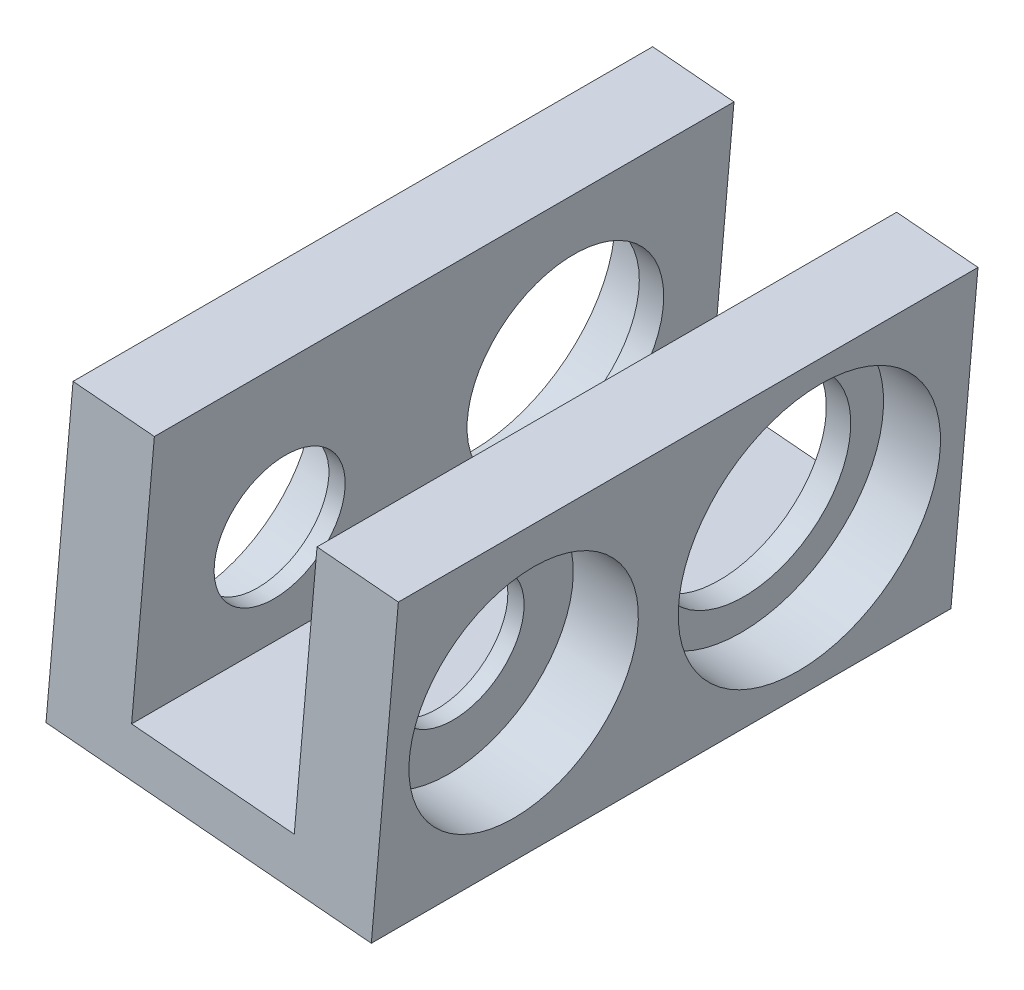
SolidWorks part; units mm, degrees
ref_plane "Front Plane" through (0, 0, 0) normal (0, 0, 1) x (1, 0, 0)
ref_plane "Top Plane" through (0, 0, 0) normal (0, 1, 0) x (1, 0, 0)
ref_plane "Right Plane" through (0, 0, 0) normal (1, 0, 0) x (0, 0, -1)
ref_axis "Axis1" through (0, 0, -88.99) along (0, 0, 1)
ref_plane "Plane1" through (0, 0, 0) normal (-0.9962, 0.0872, 0) x (0, 0, 1)
sketch "Sketch1" plane through (0, 0, 0) normal (-0.9962, 0.0872, 0) x (0, 0, 1)
  line L0 (0, 0) -> (0, 97.3301) construction
  line L9 (-88.99, 0) -> (88.99, 0) construction
  line L18 (-36.5, 38) -> (34.5, 38)
  line L19 (-36.5, 38) -> (-36.5, 0)
  line L20 (-36.5, 0) -> (34.5, 0)
  line L21 (34.5, 38) -> (34.5, 0)
  line L22 (-33.5, 19) -> (-33.5, 62.6427) construction
  line L23 (-17.5, 35) -> (44.9097, 35) construction
  line L24 (31.5, 19) -> (31.5, 63.5996) construction
  line L25 (-17.5, 3) -> (47.3057, 3) construction
  circle A0 centre (-17.5, 19) radius 12
  circle A1 centre (17.5, 19) radius 8
  circle A4 centre (-17.5, 19) radius 16 construction
  circle A5 centre (17.5, 19) radius 14 construction
  dimension "D1" = 16
  dimension "D2" = 24
  dimension "D6" = 3
  dimension "D5" = 28
  dimension "D4" = 32
  dimension "D3" = 35
  dimension "D7" = 3
  dimension "D8" = 3
  dimension "D9" = 3
extrude "Boss-Extrude1" add sketch "Sketch1" against normal blind 40
ref_plane "Plane2" through (0, 0, 0) normal (-0.0872, -0.9962, 0) x (0, 0, 1)
sketch "Sketch7" plane through (0, 0, 0) normal (-0.9962, 0.0872, 0) x (0, 0, 1)
  circle A0 centre (-17.5, 19) radius 16
  circle A1 centre (-17.5, 19) radius 12 construction
  dimension "D1" = 32
extrude "Cut-Extrude4" cut sketch "Sketch7" against normal blind 7
sketch "Sketch8" plane through (0, 0, 0) normal (-0.9962, 0.0872, 0) x (0, 0, 1)
  circle A0 centre (17.5, 19) radius 14
  circle A1 centre (17.5, 19) radius 8 construction
  dimension "D1" = 28
extrude "Cut-Extrude5" cut sketch "Sketch8" against normal blind 8
sketch "Sketch9" plane through (39.8478, -3.4862, 0) normal (0.9962, -0.0872, 0) x (0, 0, -1)
  circle A0 centre (17.5, 19) radius 16
  circle A1 centre (17.5, 19) radius 12 construction
  dimension "D1" = 32
extrude "Cut-Extrude6" cut sketch "Sketch9" against normal blind 7
sketch "Sketch10" plane through (39.8478, -3.4862, 0) normal (0.9962, -0.0872, 0) x (0, 0, -1)
  circle A0 centre (-17.5, 19) radius 14
  circle A1 centre (-17.5, 19) radius 8 construction
  dimension "D1" = 28
extrude "Cut-Extrude7" cut sketch "Sketch10" against normal blind 8
sketch "Sketch11" plane through (0, 0, 34.5) normal (0, 0, 1) x (1, 0, 0)
  line L0 (13.2739, 36.9838) -> (33.1978, 35.2407)
  line L1 (43.1597, 34.3692) -> (3.3119, 37.8554) construction
  line L2 (33.1978, 35.2407) -> (30.4088, 3.3625)
  line L4 (30.4088, 3.3625) -> (10.4849, 5.1056)
  line L5 (10.4849, 5.1056) -> (13.2739, 36.9838)
  line L6 (39.8478, -3.4862) -> (43.1597, 34.3692) construction
  line L7 (8.5316, 97.5165) -> (-8.5316, -97.5165) construction
  line L8 (-37.841, 3.3107) -> (37.841, -3.3107) construction
  point P12 (0, 0)
  point P13 (0, 0)
  dimension "D1" = 10
  dimension "D2" = 10
  dimension "D3" = 6
extrude "Cut-Extrude8" cut sketch "Sketch11" against normal through all
